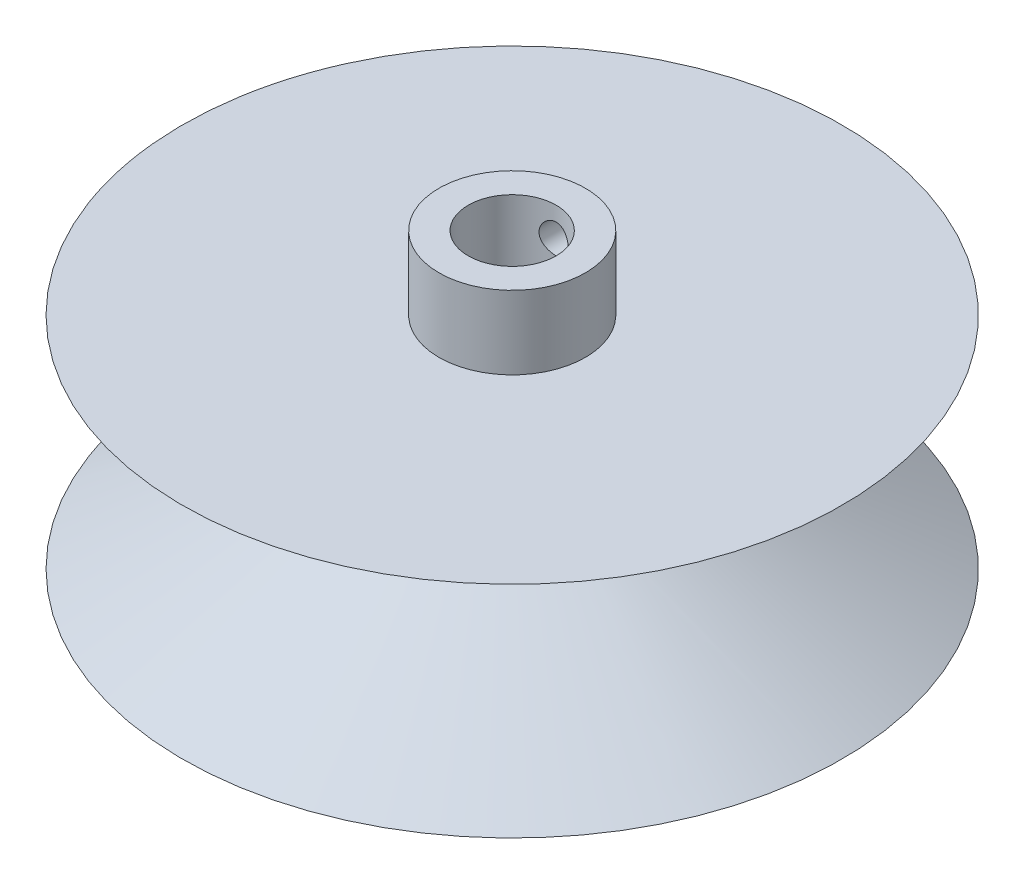
SolidWorks part; units mm, degrees
ref_plane "Front Plane" through (0, 0, 0) normal (0, 0, 1) x (1, 0, 0)
ref_plane "Top Plane" through (0, 0, 0) normal (0, 1, 0) x (1, 0, 0)
ref_plane "Right Plane" through (0, 0, 0) normal (1, 0, 0) x (0, 0, -1)
sketch "Sketch1" plane through (0, 0, 0) normal (0, 1, 0) x (1, 0, 0)
  circle A0 centre (0, 0) radius 10.25
ref_plane "Plane1" through (0, 7.5, 0) normal (0, 1, 0) x (1, 0, 0)
sketch "Sketch2" plane through (0, 7.5, 0) normal (0, 1, 0) x (1, 0, 0)
  circle A0 centre (0, 0) radius 22.5
loft "Loft1" add profiles "Sketch1", "Sketch2" connector at (9.9167, 0, 2.5927) connector at (22.488, 7.5, 0.735)
mirror "Mirror1" about plane through (0, 0, 0) normal (0, 1, 0) of "Loft1"
sketch "Sketch3" plane through (0, 7.5, 0) normal (0, 1, 0) x (1, 0, 0)
  circle A0 centre (0, 0) radius 5
extrude "Boss-Extrude1" add sketch "Sketch3" along normal blind 5
sketch "Sketch4" plane through (0, 12.5, 0) normal (0, 1, 0) x (1, 0, 0)
  circle A0 centre (0, 0) radius 3
  dimension "D1" = 6
ref_plane "Plane2" through (0, 0, -5) normal (0, 0, 1) x (1, 0, 0)
extrude "Cut-Extrude3" cut sketch "Sketch4" against normal up to surface (20 mm away) up to face at (0, -7.5, 22.5)
sketch "Sketch6" plane through (0, 0, -5) normal (0, 0, 1) x (1, 0, 0)
  line L0 (5, 12.5) -> (-5, 12.5) construction
  circle A0 centre (0, 10.5) radius 1
  dimension "D1" = 2
extrude "Cut-Extrude2" cut sketch "Sketch6" along normal up to next
